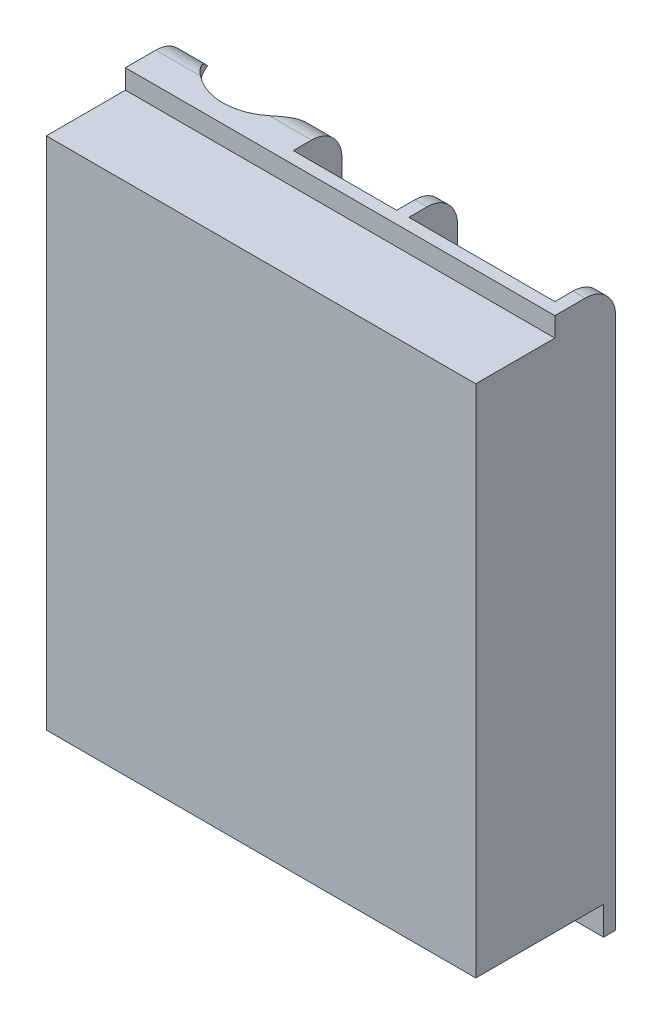
SolidWorks part; units mm, degrees
ref_plane "前视基准面" through (0, 0, 0) normal (0, 0, 1) x (1, 0, 0)
ref_plane "上视基准面" through (0, 0, 0) normal (0, 1, 0) x (1, 0, 0)
ref_plane "右视基准面" through (0, 0, 0) normal (1, 0, 0) x (0, 0, -1)
other "Configuration Table"
sketch "草图1" plane through (0, 0, 0) normal (0, 0, 1) x (1, 0, 0)
  line L0 (-74, 5) -> (-74, 90) construction
  line L1 (-73.8, 89.8) -> (-3.2, 89.8)
  line L2 (-73.8, 89.8) -> (-73.8, 5.2)
  line L3 (-73.8, 5.2) -> (-3.2, 5.2)
  line L4 (-3.2, 89.8) -> (-3.2, 5.2)
  line L5 (-3, 90) -> (-74, 90) construction
  line L6 (-3, 5) -> (-3, 90) construction
  line L7 (-3, 5) -> (-74, 5) construction
  dimension "D1" = 0.2
  dimension "D2" = 0.2
  dimension "D3" = 0.2
  dimension "D4" = 0.2
extrude "凸台-拉伸1" add sketch "草图1" against normal up to surface (23 mm away)
sketch "草图2" plane through (0, 0, -23) normal (0, 0, -1) x (-1, 0, 0)
  line L0 (82.5, 0) -> (-4, 0) construction
  line L1 (3.2, 5.2) -> (21.2, 5.2)
  line L2 (3.2, 5.2) -> (3.2, 0.5)
  line L3 (3.2, 0.5) -> (21.2, 0.5)
  line L4 (21.2, 5.2) -> (21.2, 0.5)
  line L5 (73.8, 89.8) -> (73.8, 5.2) construction
  line L6 (55.8, 5.2) -> (55.8, 0.5)
  line L7 (73.8, 0.5) -> (55.8, 0.5)
  line L8 (73.8, 5.2) -> (73.8, 0.5)
  line L9 (73.8, 5.2) -> (55.8, 5.2)
  line L10 (73.8, 5.2) -> (3.2, 5.2) construction
  dimension "D1" = 18
  dimension "D2" = 0.5
  dimension "D3" = 18
  dimension "D4" = 0.5
extrude "凸台-拉伸2" add sketch "草图2" against normal blind 2
sketch "草图3" plane through (0, 0, -23) normal (0, 0, -1) x (-1, 0, 0)
  line L0 (74, 93) -> (3, 93) construction
  line L1 (3.2, 89.8) -> (73.8, 89.8)
  line L2 (3.2, 89.8) -> (3.2, 93)
  line L3 (3.2, 93) -> (73.8, 93)
  line L4 (73.8, 89.8) -> (73.8, 93)
  point P7 (73.8, 89.8)
extrude "凸台-拉伸5" add sketch "草图3" against normal up to surface (10 mm away)
sketch "草图4" plane through (0, 5.2, 0) normal (0, -1, 0) x (1, 0, 0)
  line L0 (-73.8, -21) -> (-73.8, -23) construction
  line L1 (-3.2, -13) -> (-73.8, -13) construction
  circle A0 centre (-60.8, -25) radius 11
  point P4 (-60.8, -31.7387)
  dimension "D1" = 22
  dimension "D2" = 13
  dimension "D3" = 12
extrude "切除-拉伸1" cut sketch "草图4" against normal through all from offset 2 contours A0 offset against normal yes
sketch "草图5" plane through (0, 93, 0) normal (0, 1, 0) x (1, 0, 0)
  line L1 (-49.9833, 23) -> (-71.6167, 23)
  arc A1 (-71.6167, 23) -> (-49.9833, 23) centre (-60.8, 25) ccw
  arc A2 (-71.6167, 23) -> (-49.9833, 23) centre (-60.8, 25) ccw
  dimension "D1" = 0
extrude "拉伸-薄壁1" add sketch "草图5" against normal blind 2 thin thin type one direction reverse wall 2
other "删除面1" face at (-70.6333, 92, -23.1818) face at (-50.9667, 92, -23.1818) and patch yes
sketch "草图6" plane through (-3.2, 0, 0) normal (1, 0, 0) x (0, 0, -1)
  line L0 (23, 93) -> (15, 93)
  line L1 (13, 93) -> (23, 93) construction
  line L2 (15, 93) -> (15, 87.8)
  line L3 (15, 87.8) -> (2, 87.8)
  line L4 (2, 87.8) -> (2, 7.2)
  line L5 (2, 7.2) -> (23, 7.2)
  line L6 (23, 0.5) -> (23, 93) construction
  line L7 (23, 7.2) -> (23, 93)
  line L8 (13, 93) -> (13, 89.8) construction
  line L9 (13, 89.8) -> (0, 89.8) construction
  line L10 (0, 5.2) -> (0, 89.8) construction
  line L11 (21, 5.2) -> (0, 5.2) construction
  dimension "D1" = 2
  dimension "D2" = 2
  dimension "D3" = 2
  dimension "D4" = 2
extrude "切除-拉伸2" cut sketch "草图6" against normal blind 43 from offset 2 offset against normal yes
sketch "草图7" plane through (-5.2, 0, 0) normal (-1, 0, 0) x (0, 0, 1)
  line L6 (-23, 93) -> (-23, 7.2)
  line L7 (-23, 7.2) -> (-2, 7.2)
  line L8 (-2, 7.2) -> (-2, 87.8)
  line L9 (-2, 87.8) -> (-15, 87.8)
  line L10 (-15, 87.8) -> (-15, 93)
  line L11 (-15, 93) -> (-23, 93)
  line L12 (-23, 93) -> (-23, 7.2)
  line L13 (-23, 7.2) -> (-2, 7.2)
  line L14 (-2, 7.2) -> (-2, 87.8)
  line L15 (-2, 87.8) -> (-15, 87.8)
  line L16 (-15, 87.8) -> (-15, 93)
  line L17 (-15, 93) -> (-23, 93)
  dimension "D1" = 0
extrude "凸台-拉伸6" add sketch "草图7" along normal blind 2 from offset 24
fillet "圆角1" radius 5 4 edges at (-71.6875, 93, -23) (-50.1125, 93, -23) (-30.2, 93, -23) (-4.2, 93, -23)
